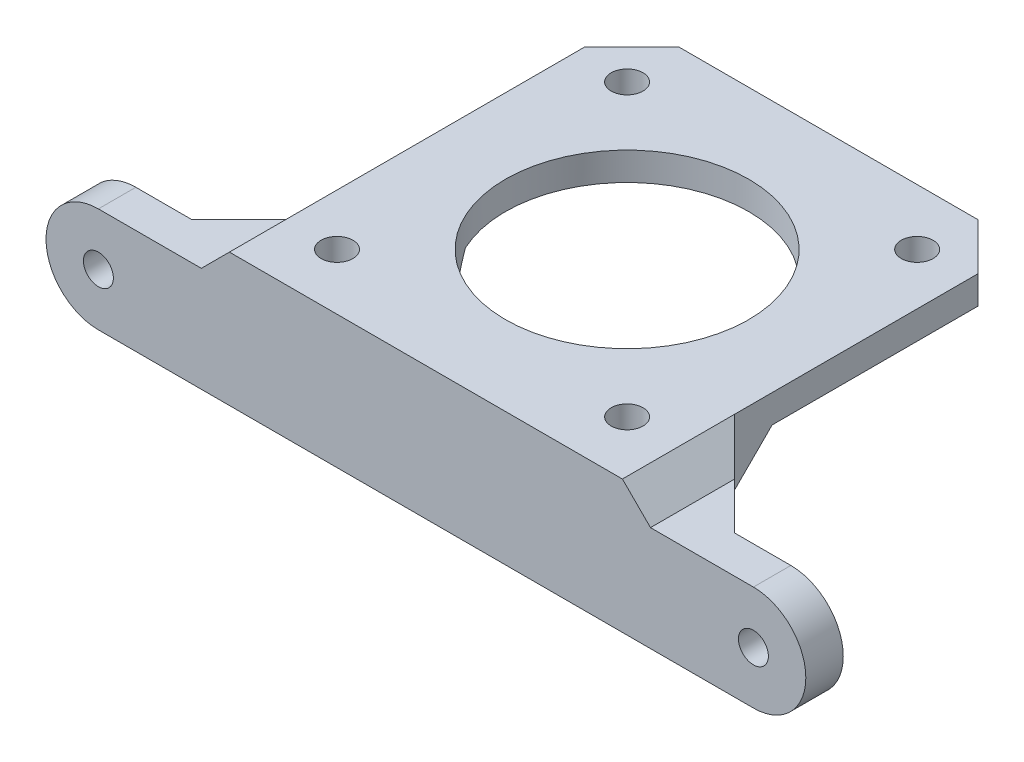
SolidWorks part; units mm, degrees
material "ABS"
ref_plane "Plano frontal" through (0, 0, 0) normal (0, 0, 1) x (1, 0, 0)
ref_plane "Plano superior" through (0, 0, 0) normal (0, 1, 0) x (1, 0, 0)
ref_plane "Plano direito" through (0, 0, 0) normal (1, 0, 0) x (0, 0, -1)
sketch "Esboço1" plane through (0, 0, 0) normal (0, 0, 1) x (1, 0, 0)
  line L0 (-35, 0) -> (35, 0) construction
  line L1 (-35, 5.6) -> (35, 5.6)
  line L2 (-35, -5.6) -> (35, -5.6)
  arc A0 (-35, 5.6) -> (-35, -5.6) centre (-35, 0) ccw
  arc A1 (35, -5.6) -> (35, 5.6) centre (35, 0) ccw
  circle A2 centre (35, 0) radius 1.6
  circle A3 centre (-35, 0) radius 1.6
  point P2 (0, 0)
  dimension "D2" = 3.2
  dimension "D3" = 4
  dimension "D1" = 70
extrude "Ressalto-extrusão1" add sketch "Esboço1" along normal blind 4
sketch "Esboço2" plane through (0, 5.6, 0) normal (0, 1, 0) x (1, 0, 0)
  line L1 (-21, 39) -> (21, 39)
  line L2 (-21, 39) -> (-21, -4)
  line L3 (-21, -4) -> (21, -4)
  line L4 (21, 39) -> (21, -4)
  line L5 (-21, 39) -> (21, -4) construction
  line L6 (-21, -4) -> (21, 39) construction
  line L7 (35, -4) -> (-35, -4) construction
  line L9 (15.5, 2) -> (-15.5, 2) construction
  line L10 (15.5, 2) -> (15.5, 33) construction
  line L11 (15.5, 33) -> (-15.5, 33) construction
  line L12 (-15.5, 2) -> (-15.5, 33) construction
  line L13 (15.5, 2) -> (-15.5, 33) construction
  line L14 (15.5, 33) -> (-15.5, 2) construction
  circle A0 centre (0, 17.5) radius 13
  circle A1 centre (-15.5, 33) radius 1.6 construction
  circle A2 centre (15.5, 33) radius 1.6 construction
  circle A3 centre (15.5, 2) radius 1.6 construction
  circle A4 centre (-15.5, 2) radius 1.6 construction
  point P0 (0, 17.5)
  point P9 (0, 17.5)
  dimension "D4" = 26
  dimension "D5" = 3.2
  dimension "D1" = 21.5
  dimension "D2" = 42
  dimension "D6" = 31
extrude "Ressalto-extrusão2" add sketch "Esboço2" along normal blind 3
chamfer "Chanfro1" distance 3 angle 45 2 edges at (21, 5.6, 2) (-21, 5.6, 2)
chamfer "Chanfro2" distance 5 angle 45 2 edges at (21, 7.1, -39) (-21, 7.1, -39)
chamfer "Chanfro3" distance 12 angle 45 1 edges at (0, 5.6, 0)
sketch "Esboço3" plane through (0, 8.6, 0) normal (0, 1, 0) x (1, 0, 0)
  line L0 (0, 17.5) -> (0, 35.0405) construction
  line L1 (0, 17.5) -> (-22.8184, 17.5) construction
  circle A0 centre (-15.5, 33) radius 1.7
  circle A1 centre (15.5, 33) radius 1.7
  circle A2 centre (15.5, 2) radius 1.7
  circle A3 centre (-15.5, 2) radius 1.7
  dimension "D3" = 3.4
  dimension "D1" = 31
  dimension "D2" = 31
extrude "Corte-extrusão1" cut sketch "Esboço3" against normal through all
sketch "Esboço4" plane through (0, 5.6, 0) normal (0, -1, 0) x (1, 0, 0)
  circle A0 centre (-15.5, -2) radius 3.5
  circle A1 centre (15.5, -2) radius 3.5
  circle A2 centre (15.5, -33) radius 3.5
  circle A3 centre (-15.5, -33) radius 3.5
  dimension "D1" = 7
extrude "Corte-extrusão2" cut sketch "Esboço4" along normal through all
chamfer "Chanfro4" distance 8 angle 45 2 edges at (21, 1.5, 0) (-21, 1.5, 0)
